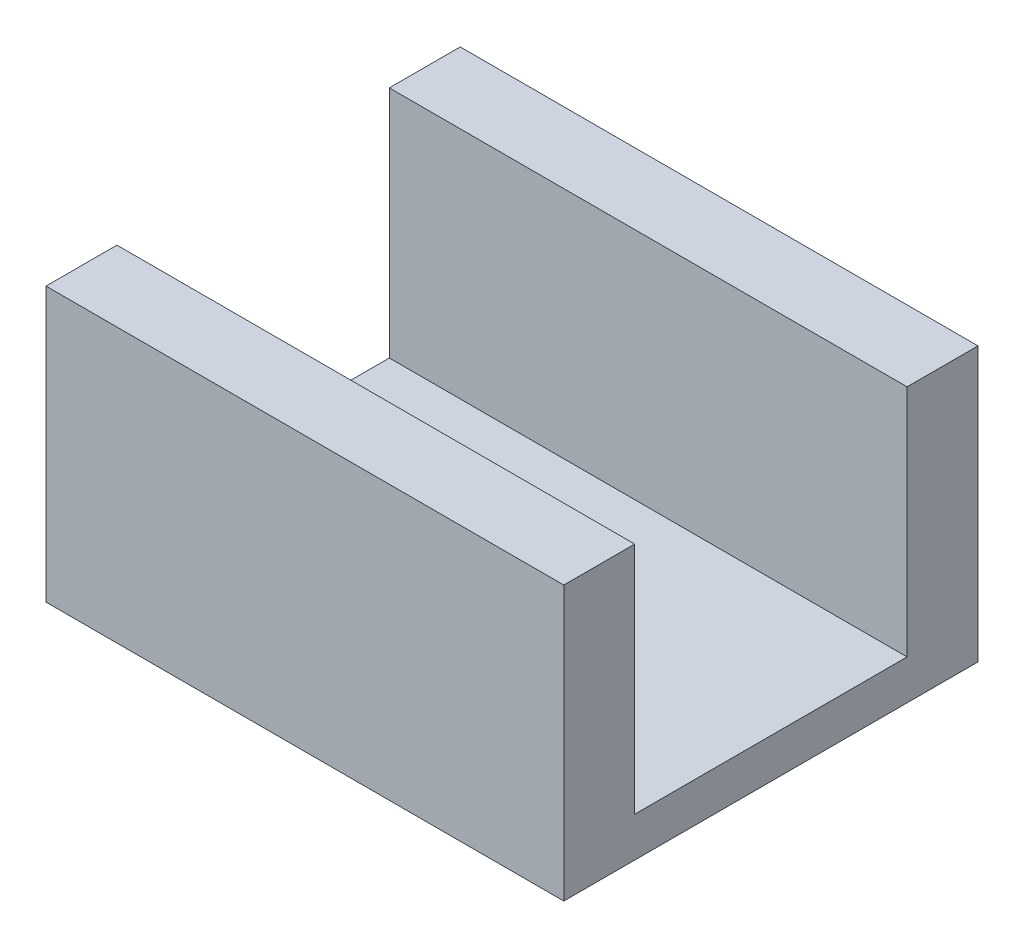
SolidWorks part; units mm, degrees
ref_plane "Front Plane" through (0, 0, 0) normal (0, 0, 1) x (1, 0, 0)
ref_plane "Top Plane" through (0, 0, 0) normal (0, 1, 0) x (1, 0, 0)
ref_plane "Right Plane" through (0, 0, 0) normal (1, 0, 0) x (0, 0, -1)
sketch "Sketch2" plane through (0, 0, 0) normal (1, 0, 0) x (0, 0, -1)
  line L0 (13.1513, 13.2155) -> (20, 13.2155)
  line L1 (-20, -13.2155) -> (20, -13.2155)
  line L2 (-20, -13.2155) -> (-20, 13.2155)
  line L3 (-20, 13.2155) -> (-13.1513, 13.2155)
  line L4 (20, -13.2155) -> (20, 13.2155)
  line L5 (-20, -13.2155) -> (20, 13.2155) construction
  line L6 (-20, 13.2155) -> (20, -13.2155) construction
  line L7 (-13.1513, -9.3744) -> (13.1513, -9.3744)
  line L8 (-13.1513, -9.3744) -> (-13.1513, 13.2155)
  line L10 (13.1513, -9.3744) -> (13.1513, 13.2155)
  line L11 (-13.1513, -9.3744) -> (13.1513, 13.2155) construction
  line L12 (-13.1513, 13.2155) -> (13.1513, -9.3744) construction
  point P0 (0, 0)
  point P6 (0, 1.9205)
  point P11 (0, 0)
  point P12 (13.1513, -9.3744)
  point P13 (20, -13.2155)
  dimension "D1" = 40
extrude "Boss-Extrude1" add sketch "Sketch2" along normal mid plane 50
